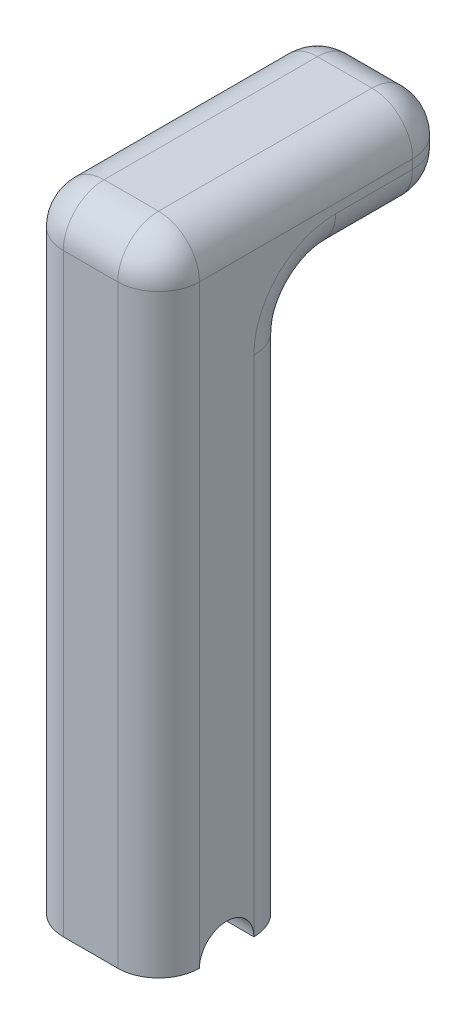
SolidWorks part; units mm, degrees
ref_plane "Front Plane" through (0, 0, 0) normal (0, 0, 1) x (1, 0, 0)
ref_plane "Top Plane" through (0, 0, 0) normal (0, 1, 0) x (1, 0, 0)
ref_plane "Right Plane" through (0, 0, 0) normal (1, 0, 0) x (0, 0, -1)
sketch "Sketch1" plane through (0, 0, 0) normal (0, 1, 0) x (1, 0, 0)
  line L1 (-123.8208, -13.4434) -> (26.1792, -13.4434)
  line L2 (-123.8208, -13.4434) -> (-123.8208, -163.4434)
  line L3 (-123.8208, -163.4434) -> (26.1792, -163.4434)
  line L4 (26.1792, -13.4434) -> (26.1792, -163.4434)
  dimension "D1" = 150
  dimension "D2" = 150
extrude "Boss-Extrude1" add sketch "Sketch1" along normal blind 700
sketch "Sketch2" plane through (0, 0, 13.4434) normal (0, 0, -1) x (-1, 0, 0)
  line L0 (123.8208, 700) -> (123.8208, 0) construction
  line L1 (-26.1792, 700) -> (123.8208, 700)
  line L2 (-26.1792, 700) -> (-26.1792, 600)
  line L3 (-26.1792, 600) -> (123.8208, 600)
  line L4 (123.8208, 700) -> (123.8208, 600)
  dimension "D1" = 100
extrude "Boss-Extrude2" add sketch "Sketch2" along normal blind 175
fillet "Fillet2" radius 45 14 edges at (26.1792, 300, 13.4434) (-123.8208, 300, 13.4434) (26.1792, 700, 0.9434) (-48.8208, 700, 163.4434) (-123.8208, 700, 0.9434) (26.1792, 600, -74.0566) (-123.8208, 600, -74.0566) (-48.8208, 600, 13.4434) (-48.8208, 700, -161.5566) (-123.8208, 650, -161.5566) (-48.8208, 600, -161.5566) (26.1792, 650, -161.5566) (-123.8208, 350, 163.4434) (26.1792, 350, 163.4434)
sketch "Sketch4" plane through (26.1792, 0, 0) normal (1, 0, 0) x (0, 0, -1)
  line L0 (-118.4434, 0) -> (-58.4434, 0) construction
  line L1 (-118.4434, 0) -> (-58.4434, 0)
  arc A0 (-118.4434, 0) -> (-58.4434, 0) centre (-88.4434, 0) cw
extrude "Cut-Extrude1" cut sketch "Sketch4" against normal through all
